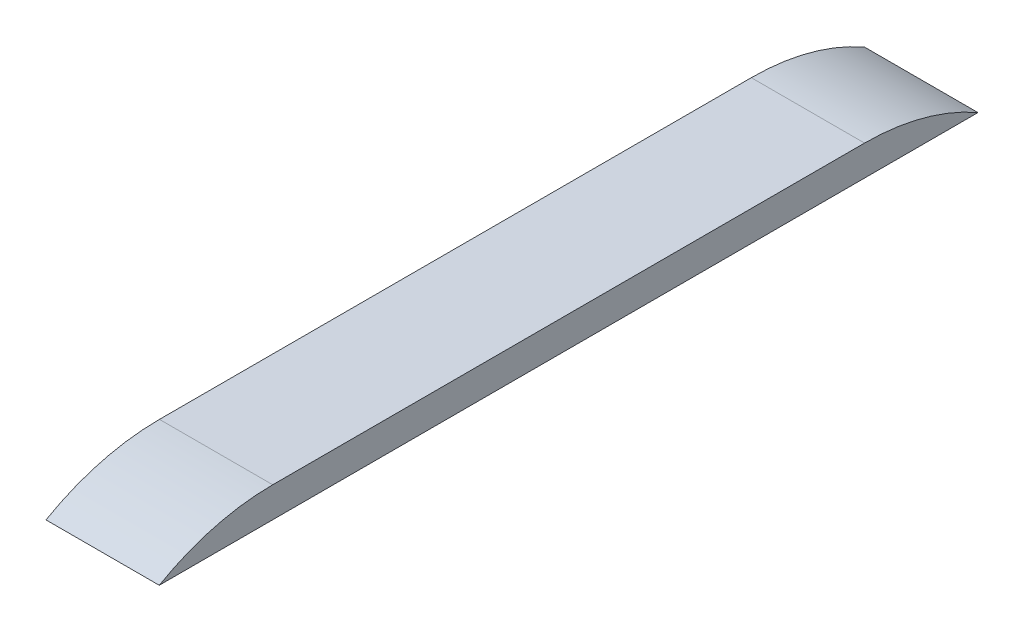
SolidWorks part; units mm, degrees
ref_plane "Спереди" through (0, 0, 0) normal (0, 0, 1) x (1, 0, 0)
ref_plane "Сверху" through (0, 0, 0) normal (0, 1, 0) x (1, 0, 0)
ref_plane "Справа" through (0, 0, 0) normal (1, 0, 0) x (0, 0, -1)
sketch "Эскиз1" plane through (0, 0, 0) normal (0, 1, 0) x (1, 0, 0)
  line L1 (-3.735, 27) -> (3.735, 27)
  line L2 (-3.735, 27) -> (-3.735, -27)
  line L3 (-3.735, -27) -> (3.735, -27)
  line L4 (3.735, 27) -> (3.735, -27)
  line L5 (-3.735, 27) -> (3.735, -27) construction
  line L6 (-3.735, -27) -> (3.735, 27) construction
  point P0 (0, 0)
extrude "Бобышка-Вытянуть1" add sketch "Эскиз1" along normal blind 2
fillet "Скругление1" radius 15 1 edges at (0, 2, 27)
fillet "Скругление2" radius 15 1 edges at (0, 2, -27)
